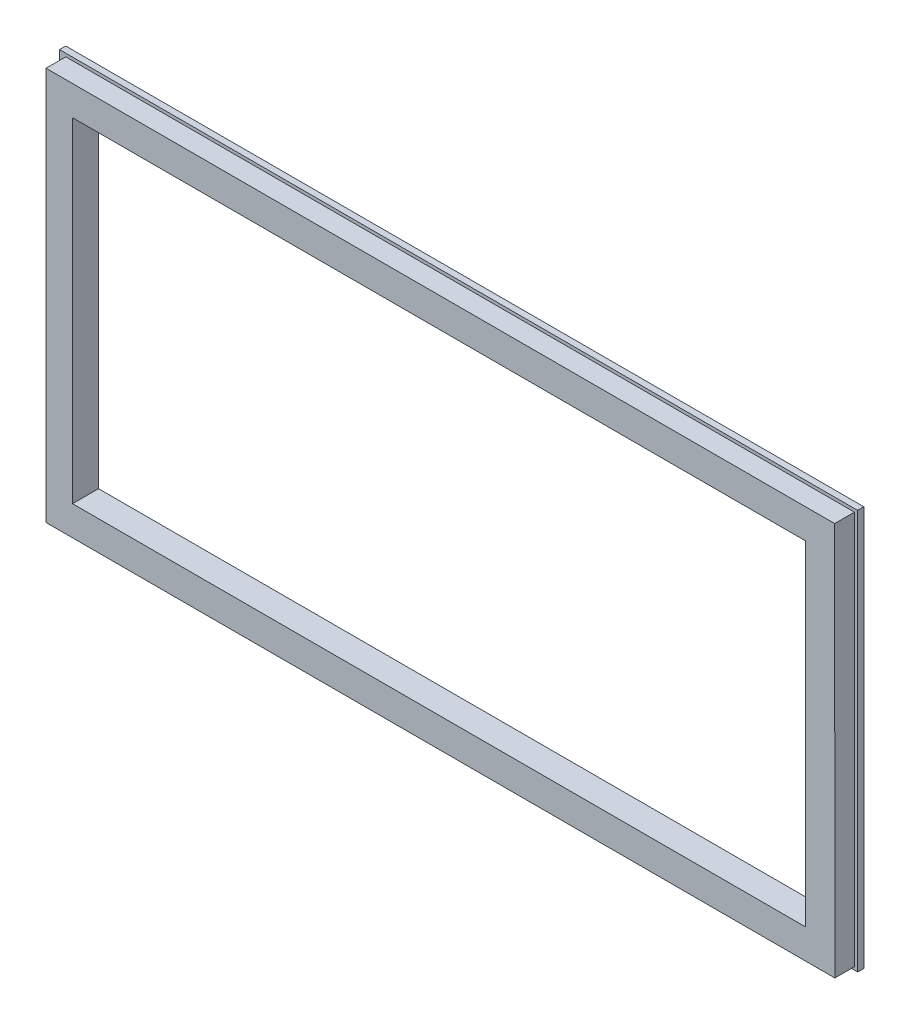
SolidWorks part; units mm, degrees
ref_plane "Front Plane" through (0, 0, 0) normal (0, 0, 1) x (1, 0, 0)
ref_plane "Top Plane" through (0, 0, 0) normal (0, 1, 0) x (1, 0, 0)
ref_plane "Right Plane" through (0, 0, 0) normal (1, 0, 0) x (0, 0, -1)
sketch "Model" plane through (0, 0, 0) normal (0, 0, 1) x (1, 0, 0)
  line L1 (-7.9049, -7.7268) -> (-7.9354, 184.294)
  line L2 (-7.9354, 184.294) -> (375.4737, 184.294)
  line L3 (375.4737, 184.294) -> (375.566, -7.7437)
  line L4 (375.566, -7.7437) -> (-7.9049, -7.7268)
  line L5 (-0.1101, 0.0729) -> (-0.1014, 176.494)
  line L6 (7.7946, 7.9723) -> (7.7873, 168.593)
  line L7 (-0.1014, 176.494) -> (367.7633, 176.494)
  line L8 (7.7873, 168.593) -> (359.8705, 168.593)
  line L9 (359.8705, 168.593) -> (359.8675, 7.9723)
  line L10 (367.7633, 176.494) -> (367.766, 0.0792)
  line L11 (359.8675, 7.9723) -> (7.7946, 7.9723)
  line L12 (367.766, 0.0792) -> (-0.1101, 0.0729)
  point P0 (0, 0)
  dimension "D1" = 352.0832
  dimension "D2" = 160.6207
  dimension "D3" = 367.8646
  dimension "D4" = 176.4211
extrude "凸台-拉伸1" add sketch "Model" along normal blind 16 contours L11 L9 L8 L6 | L4 L3 L2 L1 L10 L12 L5 L7 | L12 L10 L7 L5 L9 L11 L6 L8 region at (-3.6312, 88.2843, 0) region at (3.9742, 88.2832, 0) region at (183.83, 88.283, 0)
sketch "草图3" plane through (0, 0, 16) normal (0, 0, 1) x (1, 0, 0)
  line L2 (-6.4049, -7.7266) -> (-6.4354, 184.2942)
  line L3 (-6.4049, -7.7266) -> (-6.4354, 184.2942)
  line L17 (-6.4351, 182.794) -> (-6.4052, -6.2269)
  line L18 (-6.4052, -6.2269) -> (374.0653, -6.2436)
  line L19 (373.9744, 182.794) -> (-6.4351, 182.794)
  line L20 (374.0653, -6.2436) -> (373.9744, 182.794)
  line L21 (-6.4351, 182.794) -> (-6.4052, -6.2269)
  line L22 (-6.4052, -6.2269) -> (374.0653, -6.2436)
  line L23 (373.9744, 182.794) -> (-6.4351, 182.794)
  line L24 (374.0653, -6.2436) -> (373.9744, 182.794)
  dimension "D1" = 1.5
  dimension "D2" = 1.5
extrude "切除-拉伸-薄壁1" cut sketch "草图3" against normal blind 13 thin thin type one direction wall 1.5
extrude "切除-拉伸1" cut sketch "草图3<5>" against normal blind 3.5 contours L22 L24 L23 L3 region at (183.8027, 88.2769, 16)
sketch "草图3<5>" plane through (0, 0, 16) normal (0, 0, 1) x (1, 0, 0) same geometry as "草图3"
sketch "草图4" plane through (0, 0, 12.5) normal (0, 0, 1) x (1, 0, 0)
  line L0 (-0.1014, 176.494) -> (-0.1101, 0.0729)
  line L1 (-0.1101, 0.0729) -> (367.766, 0.0792)
  line L2 (367.766, 0.0792) -> (367.7633, 176.494)
  line L3 (367.7633, 176.494) -> (-0.1014, 176.494)
  line L4 (-0.1014, 176.494) -> (367.7633, 176.494) construction
  line L6 (7.7946, 7.9723) -> (359.8675, 7.9723)
  line L7 (359.8675, 7.9723) -> (359.8705, 168.593)
  line L8 (359.8705, 168.593) -> (7.7873, 168.593)
  line L10 (7.7873, 168.593) -> (7.7946, 7.9723)
  dimension "D1" = 176.4211
  dimension "D2" = 367.8646
extrude "切除-拉伸2" cut sketch "草图4" against normal blind 14.5 contours L10 L6 L7 L8
